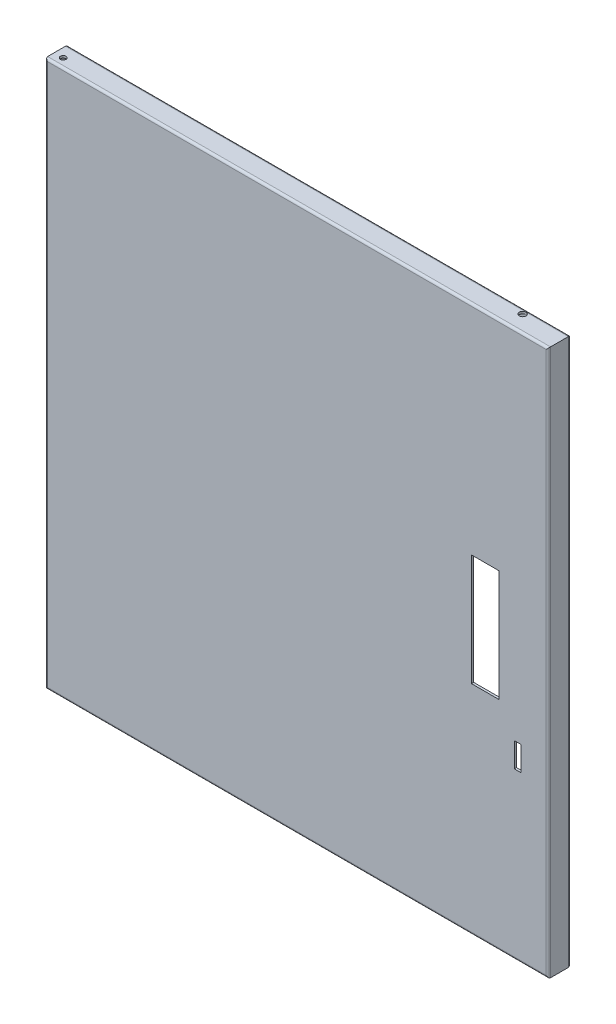
SolidWorks part; units mm, degrees
ref_plane "Front Plane" through (0, 0, 0) normal (0, 0, 1) x (1, 0, 0)
ref_plane "Top Plane" through (0, 0, 0) normal (0, 1, 0) x (1, 0, 0)
ref_plane "Right Plane" through (0, 0, 0) normal (1, 0, 0) x (0, 0, -1)
sketch "Sketch1" plane through (0, 0, 0) normal (0, 0, 1) x (1, 0, 0)
  line L1 (-225.5, 245) -> (225.5, 245)
  line L2 (-225.5, 245) -> (-225.5, -245)
  line L3 (-225.5, -245) -> (225.5, -245)
  line L4 (225.5, 245) -> (225.5, -245)
  line L5 (-225.5, 245) -> (225.5, -245) construction
  line L6 (-225.5, -245) -> (225.5, 245) construction
  point P0 (0, 0)
  dimension "D1" = 490
  dimension "D2" = 451
extrude "Boss-Extrude1" add sketch "Sketch1" along normal blind 20
sketch "Sketch2" plane through (0, 0, 0) normal (0, 0, -1) x (-1, 0, 0)
  line L0 (-225.5, 245) -> (225.5, 245) construction
  line L1 (-214.5, 234) -> (214.5, 234)
  line L2 (-214.5, 234) -> (-214.5, -234)
  line L3 (-214.5, -234) -> (214.5, -234)
  line L4 (214.5, 234) -> (214.5, -234)
  line L5 (225.5, 245) -> (225.5, -245) construction
  line L6 (225.5, -245) -> (-225.5, -245) construction
  line L7 (-225.5, -245) -> (-225.5, 245) construction
  dimension "D1" = 11
  dimension "D2" = 11
  dimension "D3" = 11
  dimension "D4" = 11
extrude "Cut-Extrude1" cut sketch "Sketch2" against normal blind 18
sketch "Sketch3" plane through (-214.5, 0, 0) normal (1, 0, 0) x (0, 0, -1)
  line L0 (-18, 234) -> (0, 234) construction
  line L1 (-18, -234) -> (-2, -234)
  line L2 (-18, -234) -> (-18, 234)
  line L3 (-18, 234) -> (-2, 234)
  line L4 (-2, -234) -> (-2, 234)
  line L5 (0, -234) -> (0, 234) construction
  dimension "D1" = 2
extrude "Cut-Extrude2" cut sketch "Sketch3" against normal blind 9
sketch "Sketch4" plane through (0, -234, 0) normal (0, 1, 0) x (1, 0, 0)
  line L0 (214.5, -18) -> (214.5, 0) construction
  line L1 (-223.5, -18) -> (214.5, -18)
  line L2 (-223.5, -18) -> (-223.5, -2)
  line L3 (-223.5, -2) -> (214.5, -2)
  line L4 (214.5, -18) -> (214.5, -2)
  line L5 (214.5, 0) -> (-214.5, 0) construction
  dimension "D1" = 2
extrude "Cut-Extrude3" cut sketch "Sketch4" against normal blind 9
sketch "Sketch5" plane through (214.5, 0, 0) normal (-1, 0, 0) x (0, 0, 1)
  line L0 (18, 234) -> (0, 234) construction
  line L1 (18, -243) -> (2, -243)
  line L2 (18, -243) -> (18, 234)
  line L3 (18, 234) -> (2, 234)
  line L4 (2, -243) -> (2, 234)
  line L5 (0, 234) -> (0, -234) construction
  dimension "D1" = 2
extrude "Cut-Extrude4" cut sketch "Sketch5" against normal blind 9
sketch "Sketch6" plane through (0, 234, 0) normal (0, -1, 0) x (1, 0, 0)
  line L0 (223.5, 18) -> (223.5, 2) construction
  line L1 (-223.5, 18) -> (223.5, 18)
  line L2 (-223.5, 18) -> (-223.5, 2)
  line L3 (-223.5, 2) -> (223.5, 2)
  line L4 (223.5, 18) -> (223.5, 2)
  line L5 (-214.5, 0) -> (214.5, 0) construction
  dimension "D1" = 2
extrude "Cut-Extrude5" cut sketch "Sketch6" against normal blind 9
sketch "Sketch7" plane through (0, 245, 0) normal (0, 1, 0) x (1, 0, 0)
  line L0 (225.5, -20) -> (-225.5, -20) construction
  line L1 (225.5, -20) -> (225.5, 0) construction
  circle A0 centre (217.5, -12) radius 2.5
  dimension "D1" = 5
  dimension "D2" = 8
  dimension "D3" = 8
sketch "Sketch8" plane through (0, 0, 20) normal (0, 0, 1) x (1, 0, 0)
  line L0 (-225.5, 245) -> (-225.5, -245) construction
  line L1 (-185.5, 35.5) -> (-152.5, 35.5)
  line L2 (-185.5, 35.5) -> (-185.5, -75.5)
  line L3 (-185.5, -75.5) -> (-152.5, -75.5)
  line L4 (-152.5, 35.5) -> (-152.5, -75.5)
  line L5 (225.5, 245) -> (-225.5, 245) construction
  point P8 (-152.5, -20)
  dimension "D1" = 73
  dimension "D2" = 111
  dimension "D3" = 33
  dimension "D4" = 265
fillet "Fillet3" radius 2 9 edges at (214.5, 0, 0) (225.5, 0, 0) (0, 245, 0) (0, -245, 0) (-225.5, 0, 0) (-225.5, 0, 20) (0, -245, 20) (225.5, 0, 20) (0, 245, 20)
fillet "Fillet4" radius 2 7 edges at (0, -243, 18) (223.5, 0, 18) (0, 243, 18) (-223.5, 0, 18) (-214.5, 0, 0) (1, -234, 0) (1, 234, 0)
sketch "Sketch12" plane through (0, 245, 0) normal (0, 1, 0) x (1, 0, 0)
  line L1 (-223.5, 0) -> (223.5, 0) construction
  line L2 (-225.5, -18) -> (-225.5, -2) construction
  circle A0 centre (-187.5, -5) radius 3
  dimension "D1" = 5
  dimension "D2" = 38
sketch "Sketch13" plane through (0, -245, 0) normal (0, -1, 0) x (1, 0, 0)
  line L0 (-225.5, 18) -> (-225.5, 2) construction
  line L1 (223.5, 0) -> (-223.5, 0) construction
  circle A0 centre (-150.5, 5) radius 3
  dimension "D1" = 75
  dimension "D2" = 5
sketch "Sketch20" plane through (0, 245, 0) normal (0, 1, 0) x (1, 0, 0)
  line L0 (-223.5, 0) -> (223.5, 0) construction
  line L1 (-225.5, -18) -> (-225.5, -2) construction
  circle A0 centre (-217.5, -12) radius 2.5
  dimension "D1" = 12
  dimension "D2" = 8
extrude "Cut-Extrude12" cut sketch "Sketch20" against normal through all
sketch "Sketch21" plane through (0, 245, 0) normal (0, 1, 0) x (1, 0, 0)
  line L0 (-223.5, 0) -> (223.5, 0) construction
  line L1 (225.5, -18) -> (225.5, -2) construction
  circle A0 centre (187.5, -5) radius 3
  dimension "D1" = 5
  dimension "D2" = 38
extrude "Cut-Extrude13" cut sketch "Sketch21" against normal up to surface (2 mm away) up to face at (-217.5, 243, 9.5)
sketch "Sketch22" plane through (0, -245, 0) normal (0, -1, 0) x (1, 0, 0)
  line L0 (225.5, 18) -> (225.5, 2) construction
  line L1 (223.5, 0) -> (-223.5, 0) construction
  circle A0 centre (150.5, 5) radius 3
  dimension "D1" = 75
  dimension "D2" = 5
extrude "Cut-Extrude14" cut sketch "Sketch22" against normal up to surface (2 mm away) up to face at (-217.5, -243, 9.5)
sketch "Sketch23" plane through (0, 0, 20) normal (0, 0, 1) x (1, 0, 0)
  line L0 (0, -8.376) -> (0, -59.5931)
  line L9 (201, -75) -> (195, -75)
  line L10 (201, -97) -> (201, -75)
  line L11 (201, -97) -> (195, -97)
  line L12 (195, -97) -> (195, -75)
  line L13 (181.5, 50) -> (156.5, 50)
  line L14 (156.5, -50) -> (156.5, 50)
  line L15 (181.5, -50) -> (156.5, -50)
  line L16 (181.5, -50) -> (181.5, 50)
extrude "Cut-Extrude15" cut sketch "Sketch23" against normal up to surface (2 mm away) contours L15 L16 L13 L14 | L12 L11 L10 L9 | L12 L9 L10 L11 region at (198, -86, 20) region at (169, 0, 20) up to face at (0, 0, 18)
